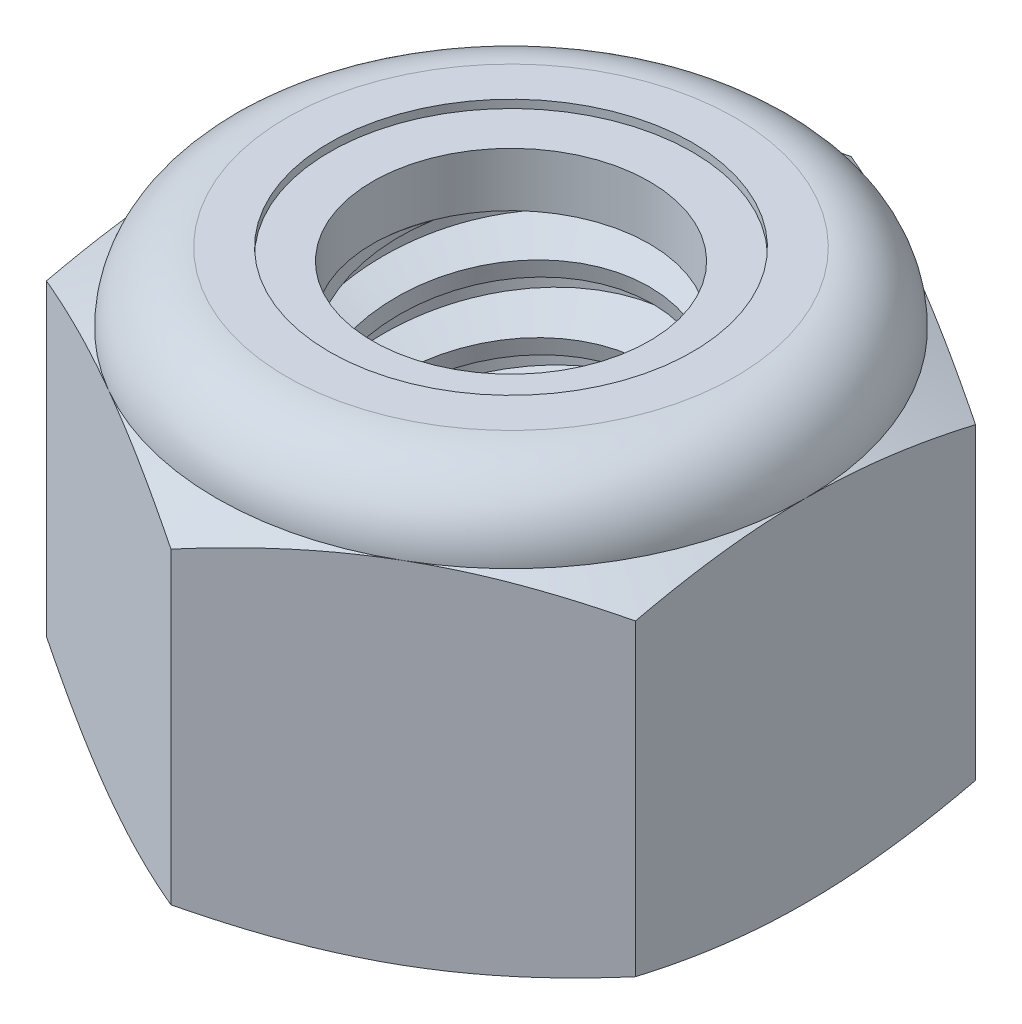
SolidWorks part; units mm, degrees
material "6061-T6 (SS)"
ref_plane "Front" through (0, 0, 0) normal (0, 0, 1) x (1, 0, 0)
ref_plane "Top" through (0, 0, 0) normal (0, 1, 0) x (1, 0, 0)
ref_plane "Right" through (0, 0, 0) normal (1, 0, 0) x (0, 0, -1)
sketch "Sketch1" plane through (0, 0, 0) normal (0, 1, 0) x (1, 0, 0)
  line L1 (0, 6.4158) -> (-5.5563, 3.2079)
  line L2 (-5.5563, 3.2079) -> (-5.5563, -3.2079)
  line L3 (-5.5563, -3.2079) -> (0, -6.4158)
  line L4 (0, -6.4158) -> (5.5562, -3.2079)
  line L5 (5.5562, -3.2079) -> (5.5562, 3.2079)
  line L6 (5.5562, 3.2079) -> (0, 6.4158)
  circle A0 centre (0, 0) radius 5.5563 construction
  dimension "Hex Flats" = 11.1125
extrude "Extrude1" add sketch "Sketch1" along normal blind 7.9375
sketch "Sketch2" plane through (0, 0, 0) normal (1, 0, 0) x (0, 0, -1)
  line L0 (-3.175, 0) -> (-3.175, 7.9375) construction
  line L1 (0, 0) -> (3.175, 0)
  line L2 (0, 0) -> (0, 7.9375)
  line L3 (0, 7.9375) -> (3.175, 7.9375)
  line L4 (3.175, 0) -> (3.175, 7.9375)
  line L5 (-3.2079, 7.9375) -> (3.2079, 7.9375) construction
  line L7 (0, -3.175) -> (0, 0) construction
  dimension "Thread Dia" = 6.35
revolve "Revolve1" add sketch "Sketch2" angle 360 about L7
sketch "Sketch3" plane through (0, 0, 0) normal (1, 0, 0) x (0, 0, -1)
  line L0 (3.175, 7.9375) -> (-3.175, 7.9375) construction
  line L1 (-3.175, 7.9375) -> (-3.175, 6.6675) construction
  line L2 (-3.175, 6.6675) -> (3.175, 7.9375) construction
  line L3 (3.175, 7.9375) -> (3.2061, 7.7818) construction
  line L4 (3.2061, 7.7818) -> (3.4241, 6.6922)
  line L5 (3.4241, 6.6922) -> (2.6722, 6.9465)
  line L6 (2.6722, 6.9465) -> (2.6099, 7.2579)
  line L7 (2.6099, 7.2579) -> (3.2061, 7.7818)
  line L8 (2.641, 7.1022) -> (3.3151, 7.237) construction
  line L9 (3.175, 7.9375) -> (3.175, 7.209) construction
  line L10 (3.175, 7.209) -> (-3.175, 5.939) construction
  line L11 (-3.175, 5.939) -> (-3.175, 6.6675) construction
  line L12 (-0.2727, 7.9375) -> (0.2727, 5.2105) construction
  line L13 (-3.175, 0) -> (-3.175, 7.9375) construction
  line L14 (0, 7.9375) -> (3.175, 7.9375) construction
  line L15 (3.175, 0) -> (3.175, 7.9375) construction
  point P13 (0, 6.574)
  dimension "D2" = 0.3175
  dimension "Thread Pitch" = 1.27
  dimension "D4" = 60
  dimension "D5" = 1.27
revolve "Cut-Revolve1" cut sketch "Sketch3" angle 360 about L12
pattern_linear "LPattern1" count 6 spacing 1.27 along (0, -1, 0) count 2 spacing 1.27 along (0, 1, 0) of "Cut-Revolve1"
sketch "Sketch4" plane through (0, 0, 0) normal (1, 0, 0) x (0, 0, -1)
  line L0 (0, 7.9375) -> (3.175, 7.9375)
  line L1 (3.175, 7.9375) -> (2.6099, 7.674)
  line L2 (2.6099, 7.674) -> (2.6099, 0.2635)
  line L3 (2.6099, 0.2635) -> (3.175, 0)
  line L4 (3.175, 0) -> (0, 0)
  line L5 (0, 0) -> (0, 7.9375)
  line L6 (3.175, 0) -> (3.175, 7.9375) construction
  line L7 (0, 7.9375) -> (3.175, 7.9375) construction
  line L8 (0, 0) -> (3.175, 0) construction
  line L9 (0, 0) -> (0, 7.9375) construction
  line L10 (0, 7.9375) -> (0, 8.561) construction
  dimension "D1" = 25
revolve "Cut-Revolve2" cut sketch "Sketch4" angle 360 about L10
combine bodies "Combine1" operation type subtract main body 112 bodies to subtract 111
sketch "Sketch5" plane through (0, 0, 0) normal (1, 0, 0) x (0, 0, -1)
  line L0 (0, 0) -> (5.5563, 0)
  line L1 (5.5563, 0) -> (6.4158, 0.4008)
  line L2 (6.4158, 0.4008) -> (6.4158, 6.2138)
  line L3 (6.4158, 6.2138) -> (5.5563, 6.6146)
  line L4 (4.2333, 7.9375) -> (4.2333, 9.2075)
  line L5 (4.2333, 9.2075) -> (7.6858, 9.2075)
  line L6 (7.6858, 9.2075) -> (7.6858, -1.27)
  line L7 (7.6858, -1.27) -> (0, -1.27)
  line L8 (0, -1.27) -> (0, 0)
  line L9 (5.5563, 6.6146) -> (5.5563, 0) construction
  line L10 (0, 0) -> (3.175, 0) construction
  line L13 (6.4158, 3.3073) -> (7.6858, 3.3073) construction
  line L14 (6.4158, 7.9375) -> (6.4158, 0) construction
  line L15 (0, 0) -> (0, 9.2075) construction
  line L20 (0, 9.2075) -> (4.2333, 9.2075) construction
  line L22 (0, 7.9375) -> (3.175, 7.9375) construction
  arc A0 (5.5563, 6.6146) -> (4.2333, 7.9375) centre (4.2333, 6.6146) ccw
  dimension "D1" = 25
  dimension "D2" = 1.27
  dimension "D3" = 7.9375
  dimension "D4" = 1.3229
revolve "Cut-Revolve3" cut sketch "Sketch5" angle 360 about L15
sketch "Sketch6" plane through (0, 0, 0) normal (1, 0, 0) x (0, 0, -1)
  line L0 (0, 6.6146) -> (5.4039, 6.6146)
  line L1 (4.2333, 7.7851) -> (3.4216, 7.7851)
  line L2 (0, 9.2075) -> (0, 6.6146)
  line L3 (3.4216, 9.2075) -> (0, 9.2075)
  line L4 (0, 9.2075) -> (4.2333, 9.2075) construction
  line L5 (0, 0) -> (0, 9.2075) construction
  line L6 (0, 9.2075) -> (0, 44.323) construction
  line L7 (3.4216, 7.7851) -> (3.4216, 9.2075)
  line L8 (4.2333, 7.9375) -> (4.2333, 7.7851) construction
  line L9 (3.4216, 7.7851) -> (2.6099, 7.7851) construction
  line L10 (2.6099, 7.7851) -> (2.6099, 7.674) construction
  arc A0 (5.4039, 6.6146) -> (4.2333, 7.7851) centre (4.2333, 6.6146) ccw
  arc A1 (5.5563, 6.6146) -> (4.2333, 7.9375) centre (4.2333, 6.6146) ccw construction
  dimension "D1" = 0.1524
revolve "Cut-Revolve4" cut sketch "Sketch6" angle 360 about L6
sketch "Sketch7" plane through (0, 0, 0) normal (1, 0, 0) x (0, 0, -1)
  line L0 (2.6099, 6.6908) -> (5.325, 6.6908)
  line L1 (4.2333, 7.7089) -> (2.6099, 7.7089)
  line L2 (2.6099, 7.7089) -> (2.6099, 6.6908)
  line L3 (2.6099, 6.6908) -> (0, 6.6908) construction
  line L4 (0, 6.6908) -> (0, 7.7089) construction
  line L5 (0, 7.7089) -> (2.6099, 7.7089) construction
  line L6 (2.6099, 6.6908) -> (2.6099, 6.6146) construction
  line L7 (0, 6.6146) -> (5.4039, 6.6146) construction
  line L8 (4.2333, 7.7089) -> (4.2333, 7.7851) construction
  arc A0 (5.325, 6.6908) -> (4.2333, 7.7089) centre (4.2333, 6.6146) ccw
  arc A2 (5.4039, 6.6146) -> (4.2333, 7.7851) centre (4.2333, 6.6146) ccw construction
  dimension "D1" = 0.0762
revolve "Revolve2" add sketch "Sketch7" angle 360 about L4
equation "\"D1@Sketch3\"=\"Thread Pitch@Sketch3\"/8"
equation "\"D2@Sketch3\"=\"Thread Pitch@Sketch3\"/4"
equation "\"D5@Sketch3\"=\"Thread Pitch@Sketch3\""
equation "\"D4@LPattern1\"=\"Thread Pitch@Sketch3\""
equation "\"D3@LPattern1\"=\"Thread Pitch@Sketch3\""
equation "\"D1@LPattern1\"=\"Height@Extrude1\"/\"Thread Pitch@Sketch3\""
equation "\"D4@Sketch5\"=\"Height@Extrude1\"/6"
